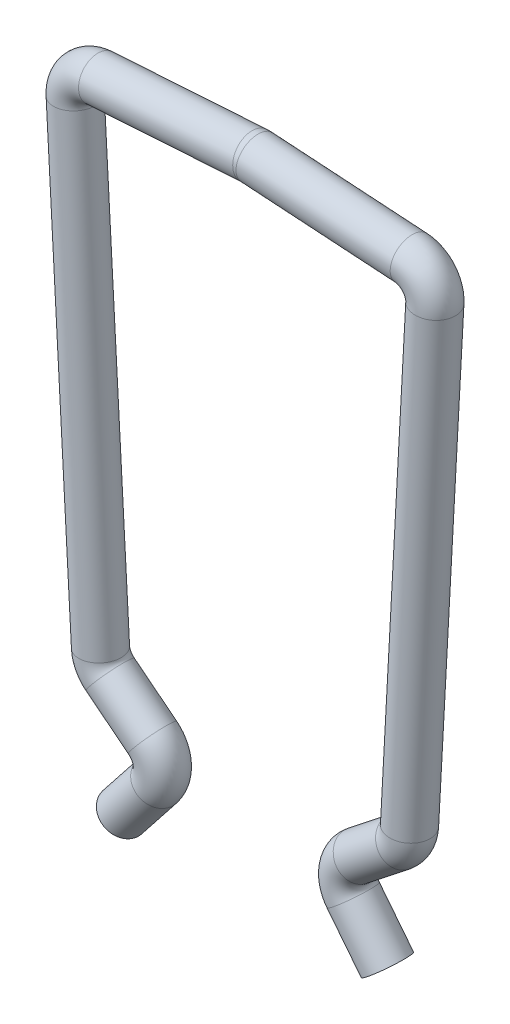
SolidWorks part; units mm, degrees
ref_plane "Front Plane" through (0, 0, 0) normal (0, 0, 1) x (1, 0, 0)
ref_plane "Top Plane" through (0, 0, 0) normal (0, 1, 0) x (1, 0, 0)
ref_plane "Right Plane" through (0, 0, 0) normal (1, 0, 0) x (0, 0, -1)
sketch "Sketch1" plane through (0, 0, 0) normal (0, 0, 1) x (1, 0, 0)
  line L0 (-0.0064, -0.0004) -> (-3.0012, -0.1936)
  line L1 (-3.0946, -0.2989) -> (-2.6025, -9.3413)
  line L2 (-2.5646, -9.4144) -> (-1.7421, -10.0642)
  line L3 (-1.5938, -11.3284) -> (-2.2593, -12.1707)
  line L4 (-2.3, -10.7704) -> (-2.987, -10.8147) construction
  line L5 (0, 0) -> (0, -12.2414) construction
  line L6 (-3.3549, -12.2414) -> (-1.7318, -12.1367) construction
  line L7 (0.0064, -0.0004) -> (3.0012, -0.1936)
  line L8 (3.3549, -12.2414) -> (1.7318, -12.1367) construction
  line L9 (2.3, -10.7704) -> (2.987, -10.8147) construction
  line L10 (1.5938, -11.3284) -> (2.2593, -12.1707)
  line L11 (2.5646, -9.4144) -> (1.7421, -10.0642)
  line L12 (3.0946, -0.2989) -> (2.6025, -9.3413)
  arc A0 (-1.5938, -11.3284) -> (-1.7421, -10.0642) centre (-2.3, -10.7704) ccw
  arc A1 (1.5938, -11.3284) -> (1.7421, -10.0642) centre (2.3, -10.7704) cw
  arc A2 (2.6025, -9.3413) -> (2.5646, -9.4144) centre (2.5026, -9.3359) cw
  arc A3 (3.0946, -0.2989) -> (3.0012, -0.1936) centre (2.9948, -0.2934) ccw
  arc A4 (0.0064, -0.0004) -> (-0.0064, -0.0004) centre (0, -0.1002) ccw
  arc A5 (-3.0946, -0.2989) -> (-3.0012, -0.1936) centre (-2.9948, -0.2934) cw
  arc A6 (-2.5646, -9.4144) -> (-2.6025, -9.3413) centre (-2.5026, -9.3359) cw
  point P23 (2.6, -9.3864)
  point P26 (3.1, -0.2)
  point P32 (-3.1, -0.2)
  point P35 (-2.6, -9.3864)
  dimension "D4" = 2.8
  dimension "D5" = 90
  dimension "D6" = 10.6
  dimension "D8" = 6.2
  dimension "D10" = 0.1
  dimension "D11" = 0.9
  dimension "D2" = 0.2
  dimension "D3" = 9.2
  dimension "D7" = 5.2
  dimension "D9" = 12
ref_plane "Plane1" through (-2.2593, -12.1707, 0) normal (-0.6199, -0.7847, 0) x (-0.7847, 0.6199, 0)
sketch "Sketch2" plane through (-2.2593, -12.1707, 0) normal (-0.6199, -0.7847, 0) x (-0.7847, 0.6199, 0)
  line L0 (0, 0) -> (0.465, 0) construction
  circle A0 centre (0.4, 0) radius 0.4
  dimension "D1" = 0.8
sweep "Sweep2" add profiles "Sketch2" path "Sketch1"
